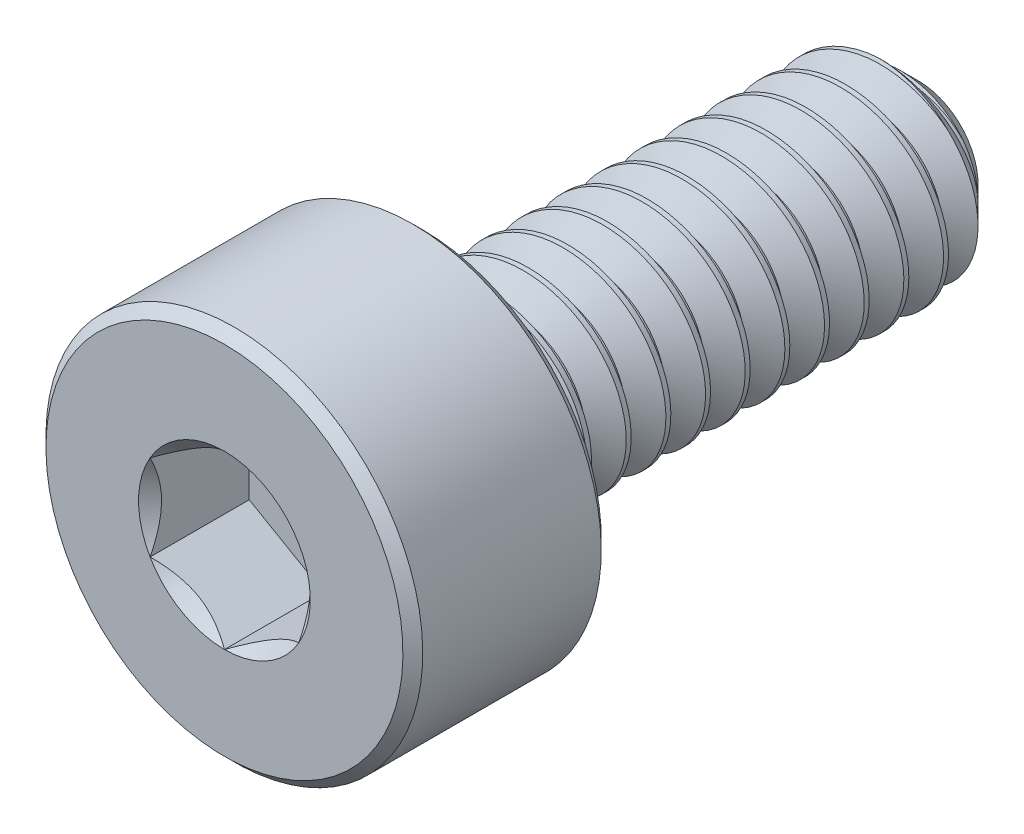
SolidWorks part; units mm, degrees
ref_plane "Front Plane" through (0, 0, 0) normal (0, 0, 1) x (1, 0, 0)
ref_plane "Top Plane" through (0, 0, 0) normal (0, 1, 0) x (1, 0, 0)
ref_plane "Right Plane" through (0, 0, 0) normal (1, 0, 0) x (0, 0, -1)
sketch "Sketch1" plane through (0, 0, 0) normal (1, 0, 0) x (0, 0, -1)
  line L0 (-3.5, 0) -> (3.5, 0) construction
  line L1 (3.5, 0) -> (3.5, 0.6) construction
  line L2 (3.5, 0.6) -> (3.1, 1) construction
  line L3 (3.1, 1) -> (3.2, 1) construction
  line L4 (3.2, 1) -> (-1.5, 1) construction
  line L5 (-1.5, 1) -> (-1.5, 1.9) construction
  line L6 (-1.5, 1.9) -> (-3.5, 1.9) construction
  line L7 (-3.5, 1.9) -> (-3.5, 0) construction
  line L8 (3.5, 0.6) -> (3.5, 1) construction
  line L9 (3.475, 1.0433) -> (3.675, 0.6969) construction
  line L10 (3.675, 0.6969) -> (3.875, 1.0433) construction
  line L11 (3.875, 1.0433) -> (3.475, 1.0433) construction
  line L12 (3.675, 1.0433) -> (3.675, 1) construction
  line L13 (3.675, 0.6969) -> (3.675, 0.7402) construction
  line L14 (3.65, 0.7402) -> (3.7, 0.7402) construction
  line L15 (3.5, 1) -> (3.85, 1) construction
  line L16 (3.4875, 1.0217) -> (3.8625, 1.0217) construction
  line L17 (3.5, 0) -> (3.5, -1) construction
  line L18 (-1.6, 1.9) -> (-1.5, 1.8) construction
  line L19 (-3.4, 1.9) -> (-3.5, 1.8) construction
  line L20 (-1.5, 1) -> (-1.5, 0) construction
  line L21 (-1.5, 0.5) -> (0.1667, 0.5) construction
  line L22 (0.1667, 0.5) -> (1.8333, 0.5) construction
  line L23 (1.8333, 0.5) -> (3.5, 0.5) construction
  line L24 (0.1667, 0.5) -> (0.1667, 1) construction
  line L25 (0.1667, 1) -> (0.1667, 1.9) construction
  line L26 (1.8333, 0.5) -> (1.8333, 1.9) construction
  point P0 (-3.5, 0.75)
  point P3 (2.5, 1)
  point P4 (0, 0)
  point P18 (1.8333, 1)
  point P22 (3.675, 0.7402)
  point P24 (3.2, 1)
  point P25 (3.675, 1)
  point P28 (3.675, 1.0217)
  point P29 (2.5, -1)
  point P30 (0.1667, 1)
  point P31 (-2.5, 1.9)
  point P37 (-1.85, 1.9)
  point P38 (-3.35, 1.9)
  point P45 (0.1667, 0.5)
  point P46 (1.8333, 0.5)
  dimension "D1" = 45
  dimension "D2" = 0.05
  dimension "D3" = 0.4
  dimension "D7" = 0.1
  dimension "D8" = 0.1
  dimension "D9" = 0.1
  dimension "D10" = 0.05
  dimension "D11" = 0.25
  dimension "Drive Size" = 1.5
  dimension "Head Diameter" = 3.8
  dimension "Head Height" = 2
  dimension "Thread Pitch" = 0.4
  dimension "Thread Major Diameter" = 2
  dimension "Length" = 5
  dimension "D12" = 0.3
  dimension "D4" = 1
sketch "Sketch2" plane through (0, 0, 0) normal (1, 0, 0) x (0, 0, -1)
  line L0 (-3.5, 0) -> (-3.5, 1.8)
  line L1 (-3.4, 1.9) -> (-1.6, 1.9)
  line L2 (-1.5, 1.8) -> (-1.5, 1)
  line L3 (-1.5, 1) -> (3.1, 1)
  line L4 (3.1, 1) -> (3.5, 0.6)
  line L5 (3.5, 0.6) -> (3.5, 0)
  line L6 (-1.6, 1.9) -> (-1.5, 1.8) construction
  line L7 (3.5, 0) -> (-3.5, 0)
  line L8 (-3.4, 1.9) -> (-3.5, 1.8) construction
  line L9 (-1.6, 1.9) -> (-1.5, 1.8)
  line L10 (-3.4, 1.9) -> (-3.5, 1.8)
revolve "Revolve1" add sketch "Sketch2" angle 360 about L7
sketch "Sketch3" plane through (0, 0, 3.5) normal (0, 0, 1) x (1, 0, 0)
  line L1 (0.75, -0.433) -> (0.75, 0.433)
  line L2 (0.75, 0.433) -> (0, 0.866)
  line L3 (0, 0.866) -> (-0.75, 0.433)
  line L4 (-0.75, 0.433) -> (-0.75, -0.433)
  line L5 (-0.75, -0.433) -> (0, -0.866)
  line L6 (0, -0.866) -> (0.75, -0.433)
  circle A0 centre (0, 0) radius 0.75 construction
extrude "Cut-Extrude1" cut sketch "Sketch3" against normal offset from surface (1 mm away) 1 up to face at (0, 1.8, 1.5)
sketch "Sketch4" plane through (0, 0, 3.5) normal (0, 0, 1) x (1, 0, 0)
  circle A0 centre (0, 0) radius 0.866
extrude "Cut-Extrude2" cut sketch "Sketch4" against normal up to vertex (1 mm away) draft 45 up to point (0, 1.9, 2.5)
ref_plane "Plane1" through (0, 0, -3.2) normal (0, 0, 1) x (1, 0, 0)
split "Split1" bodies to split 106 resulting bodies 107 108 split by face at (0, 1.8, 1.5)
sketch "Sketch6" plane through (0, 0, -3.5) normal (0, 0, -1) x (-1, 0, 0)
  circle A0 centre (0, 0) radius 1
curve "Helix/Spiral1" pitch 0.4 height 5.46 radius 1 centre (0, 0, -3.5) axis (0, 0, 1) start towards (0, 1, 0)
sketch "Sketch7" plane through (0, 0, 0) normal (1, 0, 0) x (0, 0, -1)
  line L0 (3.4875, 1.0217) -> (3.8625, 1.0217)
  line L1 (3.8625, 1.0217) -> (3.7, 0.7402)
  line L2 (3.7, 0.7402) -> (3.65, 0.7402)
  line L3 (3.65, 0.7402) -> (3.4875, 1.0217)
sweep "Cut-Sweep1" cut profiles "Sketch7" path "Helix/Spiral1" align with end faces yes
sketch "Sketch8" plane through (0, 0, 1.5) normal (0, 0, -1) x (-1, 0, 0)
  circle A0 centre (0, 0) radius 1
extrude "Boss-Extrude1" add sketch "Sketch8" along normal through all draft 45
equation "\"D2@Sketch1\" = \"Thread Pitch@Sketch1\" / 8"
equation "\"D3@Sketch1\"= \"Thread Pitch@Sketch1\""
equation "\"D4@Helix/Spiral1\" = \"Thread Pitch@Sketch1\""
equation "\"D7@Sketch1\" = \"Head Height@Sketch1\" * .05"
equation "\"D8@Sketch1\"=\"D7@Sketch1\""
equation "\"D9@Sketch1\"=\"D7@Sketch1\""
equation "\"D10@Sketch1\"=\"D7@Sketch1\"/2"
equation "\"D11@Sketch1\"=\"D10@Sketch1\"*5"
equation "\"D4@Sketch1\"=\"Thread Pitch@Sketch1\"*2.5"
equation "\"D12@Sketch1\"=\"Thread Pitch@Sketch1\"*.75"
